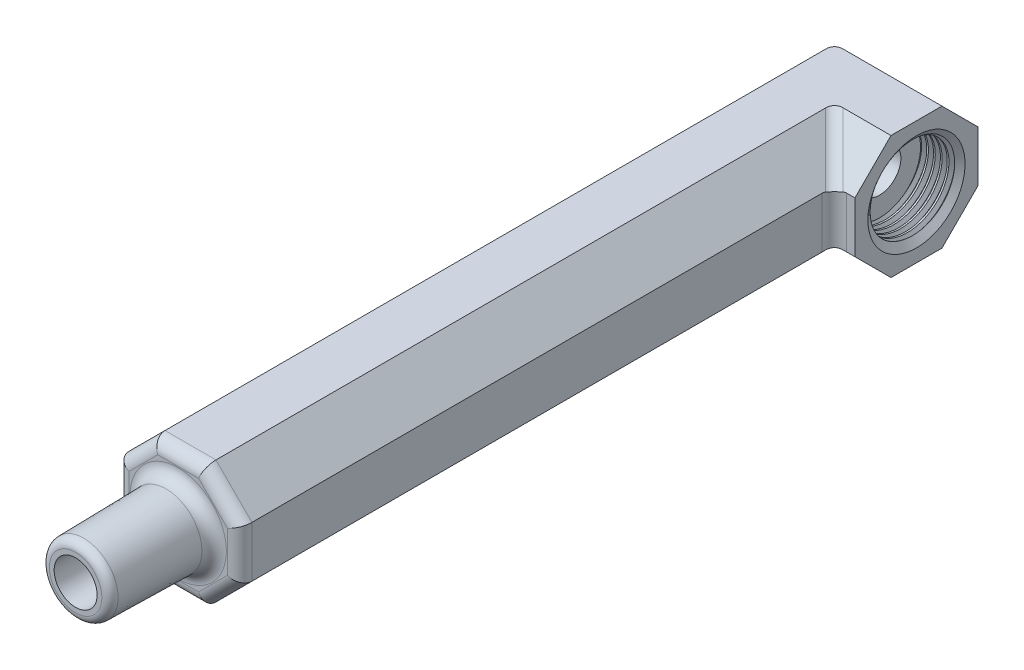
SolidWorks part; units mm, degrees
material "Plain Carbon Steel"
ref_plane "Front Plane" through (0, 0, 0) normal (0, 0, 1) x (1, 0, 0)
ref_plane "Top Plane" through (0, 0, 0) normal (0, 1, 0) x (1, 0, 0)
ref_plane "Right Plane" through (0, 0, 0) normal (1, 0, 0) x (0, 0, -1)
sketch "Sketch1" plane through (0, 0, 0) normal (0, 0, 1) x (1, 0, 0)
  circle A0 centre (0, 0) radius 5.588
  circle A1 centre (0, 0) radius 3.048
  dimension "D1" = 11.176
  dimension "D2" = 2.54
extrude "Boss-Extrude1" add sketch "Sketch1" along normal blind 15.875 draft 1
sketch "Sketch2" plane through (0, 0, 0) normal (0, 0, -1) x (-1, 0, 0)
  line L0 (3.9454, 9.525) -> (-3.9454, 9.525)
  line L1 (-3.9454, 9.525) -> (-9.525, 3.9454)
  line L2 (-9.525, 3.9454) -> (-9.525, -3.9454)
  line L3 (-9.525, -3.9454) -> (-3.9454, -9.525)
  line L4 (-3.9454, -9.525) -> (3.9454, -9.525)
  line L5 (3.9454, -9.525) -> (9.525, -3.9454)
  line L6 (9.525, -3.9454) -> (9.525, 3.9454)
  line L7 (9.525, 3.9454) -> (3.9454, 9.525)
  circle A0 centre (0, 0) radius 3.048
  circle A2 centre (0, 0) radius 3.048 construction
  point P13 (-9.525, 0)
  point P14 (0, 9.525)
  point P15 (-10.7068, 4.318)
  point P16 (0, 0)
  dimension "D1" = 135
  dimension "D2" = 19.05
extrude "Boss-Extrude2" add sketch "Sketch2" along normal blind 101.6
fillet "Fillet1" radius 1.27 1 edges at (5.3109, 0, 15.875)
sketch "Sketch3" plane through (0, 0, 0) normal (1, 0, 0) x (0, 0, -1)
  line L0 (101.6, 9.525) -> (0, 9.525) construction
  line L1 (101.6, 9.525) -> (101.6, 3.9454) construction
  line L3 (97.6546, 9.525) -> (105.5454, 9.525)
  line L4 (105.5454, 9.525) -> (111.125, 3.9454)
  line L5 (111.125, 3.9454) -> (111.125, -3.9454)
  line L6 (111.125, -3.9454) -> (105.5454, -9.525)
  line L7 (105.5454, -9.525) -> (97.6546, -9.525)
  line L8 (97.6546, -9.525) -> (92.075, -3.9454)
  line L9 (92.075, -3.9454) -> (92.075, 3.9454)
  line L10 (92.075, 3.9454) -> (97.6546, 9.525)
  point P4 (0, 0)
  point P14 (101.6, 9.525)
  dimension "D1" = 135
  dimension "D2" = 19.05
extrude "Boss-Extrude3" add sketch "Sketch3" along normal blind 12.7 and the other way blind 9.525
sketch "Sketch12" plane through (0, 0, 0) normal (0, 0, 1) x (1, 0, 0)
  line L0 (-3.9454, 9.525) -> (-9.525, 3.9454)
  line L1 (-9.525, 3.9454) -> (-9.525, -3.9454)
  line L2 (-9.525, -3.9454) -> (-3.9454, -9.525)
  line L3 (-3.9454, -9.525) -> (-11.5654, -9.525)
  line L4 (-11.5654, -9.525) -> (-11.5654, 9.525)
  line L5 (-11.5654, 9.525) -> (-3.9454, 9.525)
  dimension "D1" = 7.62
extrude "Cut-Extrude4" cut sketch "Sketch12" against normal through all
sketch "Sketch4" plane through (12.7, 0, 0) normal (1, 0, 0) x (0, 0, -1)
  line L1 (105.5454, 9.525) -> (97.6546, 9.525) construction
  line L2 (97.6546, -9.525) -> (105.5454, -9.525) construction
  line L3 (111.125, -3.9454) -> (111.125, 3.9454) construction
  circle A0 centre (101.6, 0) radius 3.302
  circle A2 centre (101.6, 0) radius 9.525 construction
  point P4 (101.3336, 0.3129)
  dimension "D1" = 6.604
extrude "Cut-Extrude1" cut sketch "Sketch4" against normal blind 17.018
fillet "Fillet12" radius 1.905 9 edges at (0, 9.525, 0) (6.7352, 6.7352, 0) (9.525, 0, 0) (6.7352, -6.7352, 0) (0, -9.525, 0) (-6.7352, -6.7352, 0) (-9.525, 0, 0) (-6.7352, 6.7352, 0) (5.588, 0, 0)
sketch "Sketch5" plane through (0, 0, 0) normal (0, 0, 1) x (1, 0, 0)
  circle A0 centre (0, 0) radius 3.2854
  circle A2 centre (0, 0) radius 3.2854 construction
  dimension "D1" = 6.5708
extrude "Cut-Extrude2" cut sketch "Sketch5" against normal blind 101.6
fillet "Fillet11" radius 1.27 1 edges at (-3.281, 0.1695, -98.3024)
sketch "Sketch8" plane through (12.7, 0, 0) normal (1, 0, 0) x (0, 0, -1)
  circle A0 centre (101.6, 0) radius 6.35
  circle A1 centre (101.6, 0) radius 3.302 construction
  point P3 (0, 0)
  point P4 (101.6, 0)
  dimension "D1" = 12.7
extrude "Cut-Extrude3" cut sketch "Sketch8" against normal blind 5.715
thread "Thread1" pitch 1.0583 method cut profile "Thread Profile1" start angle 0, offset 0, length 5.461, pitch 1.0583, diameter 12.7
ref_plane "Plane1" through (12.7, 0, -95.25) normal (0, -1, 0) x (0, 0, 1)
sketch "Thread Profile1" plane through (12.7, 0, -95.25) normal (0, -1, 0) x (0, 0, 1)
  line L0 (0, 0) -> (0, 1.0583) construction
  line L1 (0, 0) -> (0.5728, 0.3307)
  line L2 (0.5728, 0.3307) -> (0.5728, 0.463)
  line L3 (0.5728, 0.463) -> (0, 0.7937)
  line L4 (0.5728, 0.3969) -> (0, 0.3969) construction
  line L11 (0, 0) -> (0, 0.7937)
  point P2 (0, 0)
  dimension "Pitch" = 1.0583
  dimension "Profile_Angle" = 60
  dimension "Profile_Land" = 0.1323
  dimension "Profile_Height" = 0.5728
sketch "Sketch11" plane through (0, 0, 0) normal (0, 1, 0) x (1, 0, 0)
  line L0 (12.7, 101.6) -> (6.6036, 101.6) construction
  line L1 (11.8781, 107.95) -> (13.335, 110.0306)
  line L2 (13.335, 110.0306) -> (13.335, 107.95)
  line L3 (13.335, 107.95) -> (11.8781, 107.95)
  line L10 (12.7, 95.25) -> (12.7, 107.95) construction
  point P8 (12.7, 101.6)
  dimension "D1" = 35
  dimension "D2" = 6.35
  dimension "D3" = 0.635
  dimension "D4" = 2.54
revolve "Cut-Revolve1" cut sketch "Sketch11" angle 360 about L0
fillet "Fillet14" radius 1.905 6 edges at (-6.7352, -6.7352, -108.3352) (-9.525, 0, -111.125) (-6.7352, 6.7352, -108.3352) (6.7352, 6.7352, -94.8648) (9.525, 0, -92.075) (6.7352, -6.7352, -94.8648)
